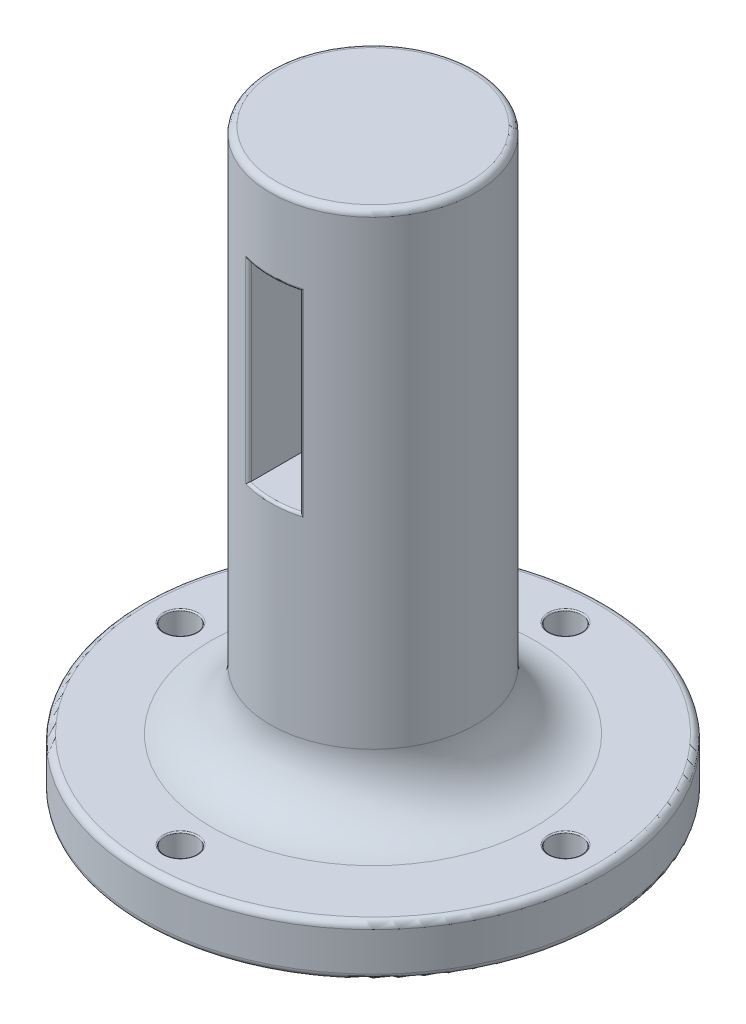
SolidWorks part; units mm, degrees
ref_plane "正面" through (0, 0, 0) normal (0, 0, 1) x (1, 0, 0)
ref_plane "平面" through (0, 0, 0) normal (0, 1, 0) x (1, 0, 0)
ref_plane "右側面" through (0, 0, 0) normal (1, 0, 0) x (0, 0, -1)
sketch "ｽｹｯﾁ1" plane through (0, 0, 0) normal (0, 0, 1) x (1, 0, 0)
  line L0 (0, 0) -> (-18, 0)
  line L1 (-18, 0) -> (-18, 4)
  line L2 (-18, 4) -> (-8, 4)
  line L3 (-8, 4) -> (-8, 45)
  line L4 (-8, 45) -> (0, 45)
  line L5 (0, 45) -> (0, 0)
  dimension "D1" = 18
  dimension "D2" = 45
  dimension "D3" = 8
  dimension "D4" = 4
revolve "回転1" add sketch "ｽｹｯﾁ1" angle 360 about L5
sketch "ｽｹｯﾁ3" plane through (0, 0, 0) normal (0, -1, 0) x (1, 0, 0)
  circle A0 centre (0, 15) radius 1.25
  circle A1 centre (15, 0) radius 1.25
  circle A2 centre (0, -15) radius 1.25
  circle A3 centre (-15, 0) radius 1.25
  dimension "D1" = 2.5
  dimension "D2" = 2.5
  dimension "D3" = 2.5
  dimension "D4" = 2.5
  dimension "D5" = 15
  dimension "D6" = 15
  dimension "D7" = 15
  dimension "D8" = 15
extrude "ｶｯﾄ - 押し出し1" cut sketch "ｽｹｯﾁ3" against normal through all
fillet "ﾌｨﾚｯﾄ3" radius 0.5 3 edges at (-18, 0, 0) (-18, 4, 0) (-8, 45, 0)
fillet "ﾌｨﾚｯﾄ4" radius 4.6 1 edges at (-8, 4, 0)
fillet "ﾌｨﾚｯﾄ6" radius 0.1 4 edges at (-1.25, 4, 15) (13.75, 4, 0) (-1.25, 4, -15) (-16.25, 4, 0)
fillet "ﾌｨﾚｯﾄ7" radius 0.1 4 edges at (-13.75, 0, 0) (1.25, 0, -15) (16.25, 0, 0) (1.25, 0, 15)
sketch "ｽｹｯﾁ5" plane through (0, 0, 0) normal (0, 0, 1) x (1, 0, 0)
  line L1 (-2, 38.7663) -> (2, 38.7663)
  line L2 (-2, 38.7663) -> (-2, 23.7663)
  line L3 (-2, 23.7663) -> (2, 23.7663)
  line L4 (2, 38.7663) -> (2, 23.7663)
  point P7 (0, 23.7663)
  dimension "D1" = 4
  dimension "D2" = 15
extrude "ｶｯﾄ - 押し出し3" cut sketch "ｽｹｯﾁ5" against normal through all and the other way through all
fillet "ﾌｨﾚｯﾄ10" radius 0.2 4 edges at (0, 23.7663, 8) (-2, 31.2663, 7.746) (2, 31.2663, 7.746) (0, 38.7663, 8)
fillet "ﾌｨﾚｯﾄ11" radius 0.2 4 edges at (2, 31.2663, -7.746) (0, 23.7663, -8) (-2, 31.2663, -7.746) (0, 38.7663, -8)
